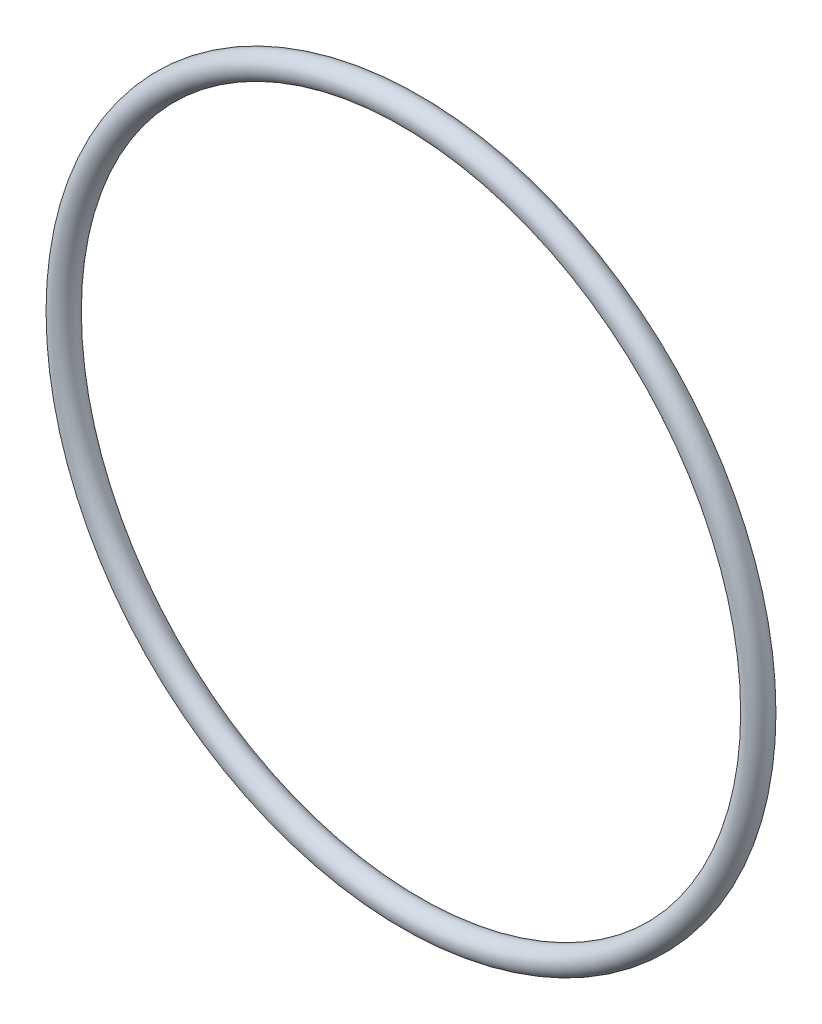
SolidWorks part; units mm, degrees
ref_plane "Front" through (0, 0, 0) normal (0, 0, 1) x (1, 0, 0)
ref_plane "Top" through (0, 0, 0) normal (0, 1, 0) x (1, 0, 0)
ref_plane "Right" through (0, 0, 0) normal (1, 0, 0) x (0, 0, -1)
sketch "Sketch1" plane through (0, 0, 0) normal (1, 0, 0) x (0, -1, 0)
  line L0 (0, -1.25) -> (0, 1.25) construction
  line L2 (-39.6, 0) -> (39.6, 0) construction
  line L3 (-33.5, 0) -> (33.5, 0) construction
  circle A0 centre (34.75, 0) radius 1.25
  point P9 (33.5, 0)
  point P10 (36, 0)
  point P13 (34.75, 1.25)
  point P14 (34.75, -1.25)
  dimension "Width" = 2.5
  dimension "ID" = 67
revolve "Revolve1" add sketch "Sketch1" angle 360 about L0
ref_axis "Axis1" through (0, 0, -1.375) along (0, 0, 1)
ref_plane "Plane1" through (0, 0, -1.5) normal (0, 0, 1) x (1, 0, 0)
